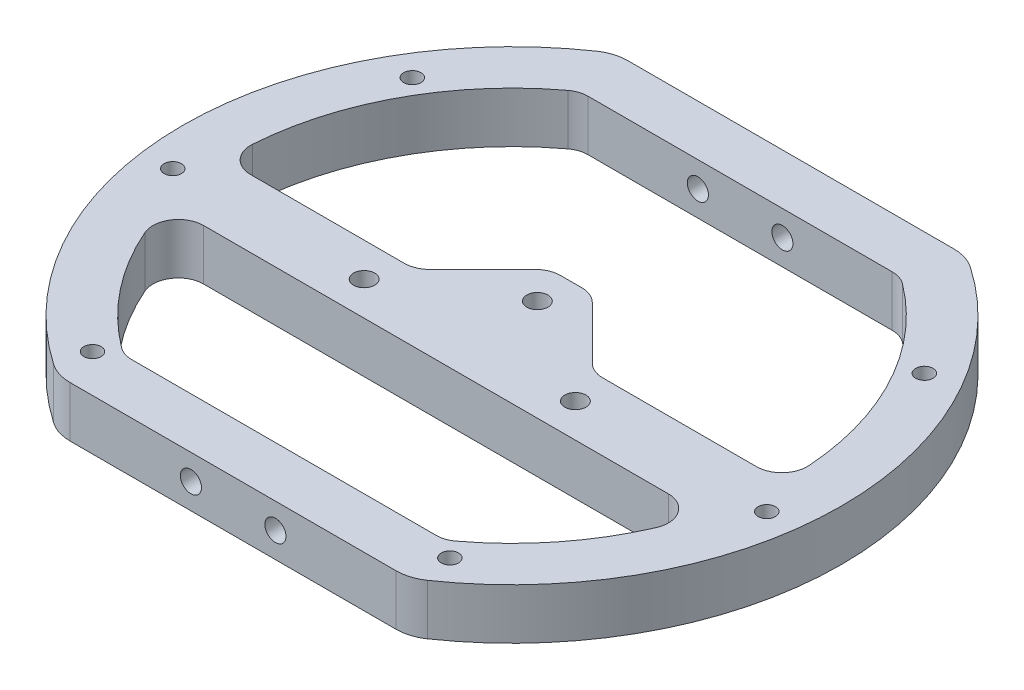
SolidWorks part; units mm, degrees
ref_plane "Front Plane" through (0, 0, 0) normal (0, 0, 1) x (1, 0, 0)
ref_plane "Top Plane" through (0, 0, 0) normal (0, 1, 0) x (1, 0, 0)
ref_plane "Right Plane" through (0, 0, 0) normal (1, 0, 0) x (0, 0, -1)
sketch "Sketch1" plane through (0, 0, 0) normal (0, 1, 0) x (1, 0, 0)
  line L0 (-20.7846, 33) -> (20.7846, 33)
  line L1 (-20.7846, -33) -> (20.7846, -33)
  line L2 (0, 33) -> (0, -33) construction
  arc A0 (-20.7846, 33) -> (-20.7846, -33) centre (0, 0) ccw
  arc A1 (20.7846, -33) -> (20.7846, 33) centre (0, 0) ccw
  point P9 (0, 0)
  dimension "D1" = 78
  dimension "D2" = 66
extrude "Boss-Extrude1" add sketch "Sketch1" along normal blind 6
fillet "Fillet1" radius 5 4 edges at (-20.7846, 3, -33) (20.7846, 3, -33) (-20.7846, 3, 33) (20.7846, 3, 33)
hole_wizard "M3x0.5 Tapped Hole1" positions "Sketch2" profile "Sketch3" tap size "M3x0.5" standard "ANSI Metric"
sketch "Sketch2" plane through (0, 0, 33) normal (0, 0, 1) x (1, 0, 0)
  line L0 (0, 0) -> (0, 6) construction
  line L1 (-19.2873, 0) -> (19.2873, 0) construction
  line L2 (-19.2873, 6) -> (19.2873, 6) construction
  line L5 (-5, 3) -> (5, 3) construction
  point P0 (-5, 3)
  point P2 (5, 3)
  point P18 (0, 3)
  dimension "D1" = 10
sketch "Sketch3" plane through (-5, 3, 33) normal (1, 0, 0) x (0, -1, 0)
  line L0 (0, 0) -> (0, 8.2511)
  line L1 (0, 8.2511) -> (1.25, 7.5)
  line L2 (1.25, 7.5) -> (1.25, 0)
  line L5 (1.25, 0) -> (0, 0)
  line L10 (0, 8.2511) -> (-1.25, 7.5) construction
  line L11 (0, -6.35) -> (0, 107.95) construction
  dimension "Tap Drill Dia." = 2.5
  dimension "Tap Drill Depth" = 7.5
  dimension "Drill Angle" = 118
cosmetic thread "Hole Thread1" parameters "D1"=6, "D2"=3
cosmetic thread "Hole Thread2" parameters "D1"=6, "D2"=3
mirror "Mirror1" about plane through (0, 0, 0) normal (0, 0, 1) of "M3x0.5 Tapped Hole1"
cosmetic thread "Hole Thread3" parameters "D1"=6, "D2"=3
cosmetic thread "Hole Thread4" parameters "D1"=6, "D2"=3
hole_wizard "M3x0.5 Tapped Hole2" positions "Sketch4" profile "Sketch5" tap size "M3x0.5" standard "ANSI Metric" end condition through all
sketch "Sketch4" plane through (0, 0, 0) normal (0, -1, 0) x (-1, 0, 0)
  line L0 (12.5, -5) -> (-12.5, -5) construction
  point P0 (12.5, -5)
  point P2 (-12.5, -5)
  point P8 (0, -5)
  point P10 (0, 3)
  dimension "D1" = 25
  dimension "D2" = 5
  dimension "D3" = 8
sketch "Sketch5" plane through (-12.5, 0, 5) normal (1, 0, 0) x (0, 0, -1)
  line L0 (0, 0) -> (0, 6)
  line L1 (0, 6) -> (1.25, 6)
  line L2 (1.25, 6) -> (1.25, 0)
  line L5 (1.25, 0) -> (0, 0)
  line L11 (0, -6.35) -> (0, 107.95) construction
  dimension "Thru Tap Drill Dia." = 2.5
  dimension "Thru Tap Drill Depth" = 6
cosmetic thread "Hole Thread5" parameters "D2"=3
cosmetic thread "Hole Thread6" parameters "D2"=3
cosmetic thread "Hole Thread7" parameters "D2"=3
sketch "Sketch6" plane through (0, 0, 0) normal (0, -1, 0) x (1, 0, 0)
  line L2 (-31.749, 9) -> (31.749, 9)
  line L3 (32.9848, 1) -> (10.5, 1)
  line L4 (-18.9737, -27) -> (18.9737, -27)
  line L5 (18.9737, 27) -> (-18.9737, 27)
  line L6 (-18.9737, -27) -> (18.9737, -27)
  line L7 (18.9737, 27) -> (-18.9737, 27)
  line L8 (-32.619, 5) -> (32.619, 5) construction
  line L10 (-10.5, 1) -> (-2.5, -7)
  line L11 (2.5, -7) -> (10.5, 1)
  line L12 (-10.5, 1) -> (-32.9848, 1)
  line L13 (-2.5, -7) -> (2.5, -7)
  line L14 (0, -7) -> (0, 0) construction
  arc A0 (-32.9848, 1) -> (-18.9737, -27) centre (0, 0) ccw
  arc A1 (31.749, 9) -> (18.9737, 27) centre (0, 0) ccw
  arc A12 (-18.9737, 27) -> (-18.9737, -27) centre (0, 0) ccw
  arc A13 (18.9737, -27) -> (18.9737, 27) centre (0, 0) ccw
  arc A14 (-18.9737, 27) -> (-31.749, 9) centre (0, 0) ccw
  arc A15 (18.9737, -27) -> (32.9848, 1) centre (0, 0) ccw
  point P6 (-12.5, 5)
  point P9 (0, 0)
  dimension "D2" = 8
  dimension "D3" = 8
  dimension "D4" = 5
  dimension "D1" = 6
extrude "Cut-Extrude1" cut sketch "Sketch6" against normal up to surface (6 mm away) up to face at (-12.5, 6, 3.75)
fillet "Fillet2" radius 3 12 edges at (18.9737, 3, -27) (-18.9737, 3, -27) (32.9848, 3, 1) (-31.749, 3, 9) (18.9737, 3, 27) (31.749, 3, 9) (-18.9737, 3, 27) (-32.9848, 3, 1) (-10.5, 3, 1) (10.5, 3, 1) (-2.5, 3, -7) (2.5, 3, -7)
hole_wizard "M2.5x0.45 Tapped Hole1" positions "Sketch7" profile "Sketch8" tap size "M2.5x0.45" standard "ANSI Metric" end condition through all
sketch "Sketch7" plane through (0, 0, 0) normal (0, -1, 0) x (-1, 0, 0)
  point P0 (-21.15, -28.5)
  point P3 (21.15, -28.5)
  point P6 (30.3, 18.5)
  point P9 (-30.3, 18.5)
  point P12 (-35.15, -5)
  point P30 (35.15, -5)
sketch "Sketch8" plane through (21.15, 0, 28.5) normal (1, 0, 0) x (0, 0, -1)
  line L0 (0, 0) -> (0, 6)
  line L1 (0, 6) -> (1.025, 6)
  line L2 (1.025, 6) -> (1.025, 0)
  line L5 (1.025, 0) -> (0, 0)
  line L11 (0, -6.35) -> (0, 107.95) construction
  dimension "Thru Tap Drill Dia." = 2.05
  dimension "Thru Tap Drill Depth" = 6
cosmetic thread "Hole Thread8" parameters "D2"=2.5
cosmetic thread "Hole Thread9" parameters "D2"=2.5
cosmetic thread "Hole Thread10" parameters "D2"=2.5
cosmetic thread "Hole Thread11" parameters "D2"=2.5
cosmetic thread "Hole Thread12" parameters "D2"=2.5
cosmetic thread "Hole Thread13" parameters "D2"=2.5
